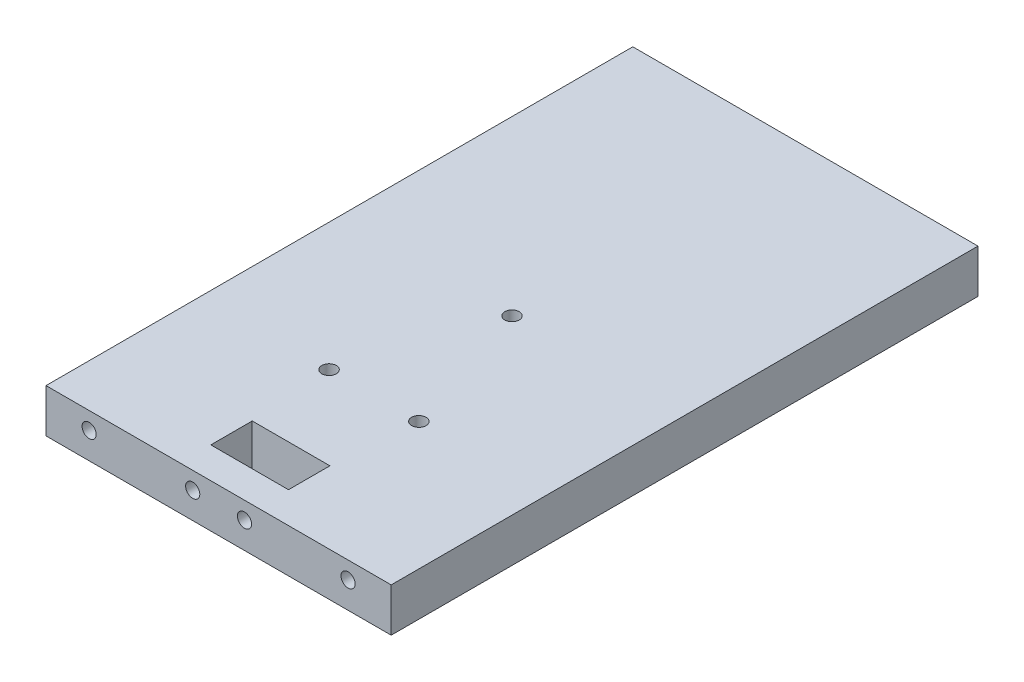
SolidWorks part; units mm, degrees
ref_plane "Front Plane" through (0, 0, 0) normal (0, 0, 1) x (1, 0, 0)
ref_plane "Top Plane" through (0, 0, 0) normal (0, 1, 0) x (1, 0, 0)
ref_plane "Right Plane" through (0, 0, 0) normal (1, 0, 0) x (0, 0, -1)
sketch "Sketch1" plane through (0, 0, 0) normal (0, 0, 1) x (1, 0, 0)
  line L0 (37.5, 0) -> (-37.5, 0) construction
  line L1 (-50, 5) -> (50, 5)
  line L2 (-50, 5) -> (-50, -5)
  line L3 (-50, -5) -> (50, -5) construction
  line L4 (50, 5) -> (50, -5)
  line L5 (-50, 5) -> (50, -5) construction
  line L6 (-50, -5) -> (50, 5) construction
  line L8 (-50, -5) -> (50, -5) construction
  line L9 (-50, -5) -> (-50, -7.63)
  line L10 (-50, -7.63) -> (50, -7.63)
  line L11 (50, -5) -> (50, -7.63)
  circle A0 centre (-37.5, 0) radius 2.05
  circle A1 centre (-22.5, 0) radius 2.05 [skipped]
  circle A2 centre (-7.5, 0) radius 2.05
  circle A3 centre (7.5, 0) radius 2.05
  circle A4 centre (22.5, 0) radius 2.05 [skipped]
  circle A5 centre (37.5, 0) radius 2.05
  point P0 (0, 0)
  point P9 (0, 0)
  dimension "D4" = 4.1
  dimension "D1" = 75
  dimension "D2" = 100
  dimension "D3" = 10
  dimension "D6" = 2.63
  dimension "D5" = 6
extrude "Boss-Extrude1" add sketch "Sketch1" along normal blind 170
extrude "Boss-Extrude3" add sketch "Sketch1<3>" along normal offset from surface (151 mm away) 9 from offset 10 contours A0 | A2 | A3 | A5 region at (-37.5, 0, 0) region at (-7.5, 0, 0) region at (7.5, 0, 0) region at (37.5, 0, 0) up to face at (9.55, 0, 170)
sketch "Sketch1<3>" plane through (0, 0, 0) normal (0, 0, 1) x (1, 0, 0) same geometry as "Sketch1"
sketch "Sketch3" plane through (0, 5, 0) normal (0, 1, 0) x (1, 0, 0)
  line L0 (0, 0) -> (0, -170) construction
  line L1 (50, -170) -> (-50, -170) construction
  line L2 (13, -125) -> (-13, -125) construction
  line L4 (-11.25, -149) -> (11.25, -149)
  line L5 (-11.25, -149) -> (-11.25, -161)
  line L6 (-11.25, -161) -> (11.25, -161)
  line L7 (11.25, -149) -> (11.25, -161)
  line L8 (-11.25, -149) -> (11.25, -161) construction
  line L9 (-11.25, -161) -> (11.25, -149) construction
  circle A0 centre (0, -85) radius 2.1
  circle A1 centre (13, -125) radius 2.1
  circle A2 centre (-13, -125) radius 2.1
  point P8 (0, -125)
  point P12 (0, -155)
  dimension "D3" = 4.2
  dimension "D4" = 4.2
  dimension "D5" = 4.2
  dimension "D1" = 45
  dimension "D2" = 26
  dimension "D6" = 40
  dimension "D7" = 12
  dimension "D8" = 22.5
  dimension "D9" = 30
extrude "Cut-Extrude1" cut sketch "Sketch3" against normal through all
